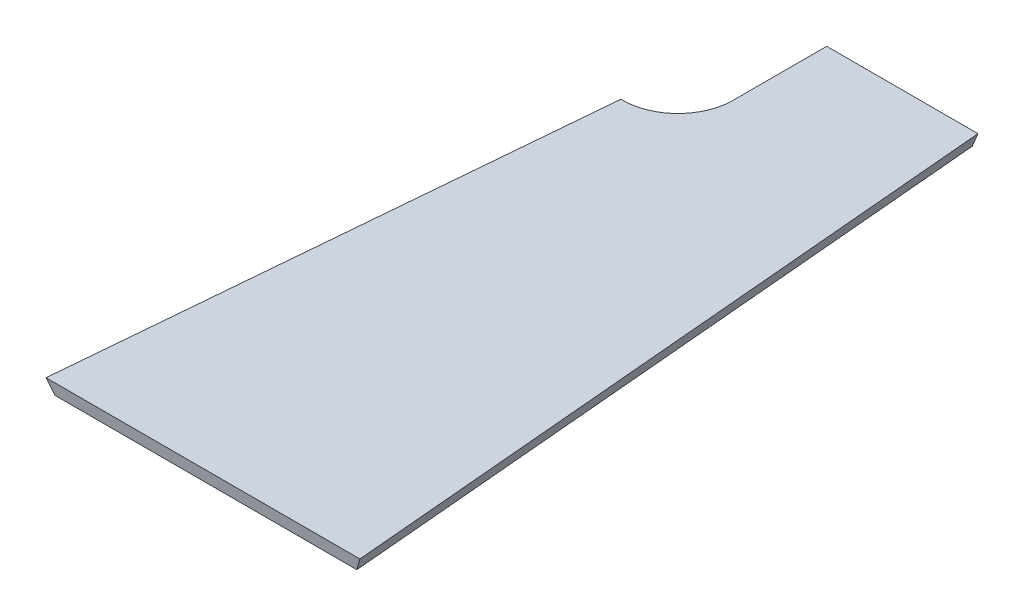
SolidWorks part; units mm, degrees
ref_plane "Ebene vorne" through (0, 0, 0) normal (0, 0, 1) x (1, 0, 0)
ref_plane "Ebene oben" through (0, 0, 0) normal (0, 1, 0) x (1, 0, 0)
ref_plane "Ebene rechts" through (0, 0, 0) normal (1, 0, 0) x (0, 0, -1)
sketch "Skizze1" plane through (0, 0, 0) normal (0, 1, 0) x (1, 0, 0)
  line L1 (-28.5, -61.5) -> (28.5, -61.5)
  line L2 (-28.5, -61.5) -> (-28.5, 61.5)
  line L3 (-28.5, 61.5) -> (28.5, 61.5)
  line L4 (28.5, -61.5) -> (28.5, 61.5)
  line L5 (-28.5, -61.5) -> (28.5, 61.5) construction
  line L6 (-28.5, 61.5) -> (28.5, -61.5) construction
  point P0 (0, 0)
  dimension "D1" = 57
  dimension "D2" = 123
extrude "Aufsatz-Linear austragen1" add sketch "Skizze1" along normal blind 2.5
sketch "Skizze2" plane through (28.5, 0, 0) normal (1, 0, 0) x (0, 0, -1)
  line L0 (-61.5, 2.5) -> (-61.5, 0)
  line L1 (55, 0) -> (-55, 0) construction
  line L2 (-61.5, 2.5) -> (-61.5, 0) construction
  line L3 (-61.5, 0) -> (-60.9686, 0)
  line L4 (-60.9686, 0) -> (-61.5, 2.5)
  dimension "D1" = 102
extrude "Schnitt-Linear austragen1" cut sketch "Skizze2" against normal through all
sketch "Skizze3" plane through (0, 2.5, 0) normal (0, 1, 0) x (1, 0, 0)
  line L0 (-28.5, -61.5) -> (-17.7389, 61.5)
  line L1 (28.5, 61.5) -> (-28.5, 61.5) construction
  line L2 (-17.7389, 61.5) -> (-28.5, 61.5)
  line L3 (-28.5, 61.5) -> (-28.5, -61.5)
  line L4 (28.5, -61.5) -> (17.7389, 61.5)
  line L5 (17.7389, 61.5) -> (28.5, 61.5)
  line L6 (28.5, 61.5) -> (28.5, -61.5)
  dimension "D1" = 95
  dimension "D2" = 95
extrude "Schnitt-Linear austragen2" cut sketch "Skizze3" against normal through all
ref_axis "Achse1" through (23.1194, 2.5, 0) along (0, -1, 0)
ref_plane "Ebene1" through (0.1756, 0, 2.0073) normal (0.0872, 0, 0.9962) x (0, -1, 0)
sketch "Skizze5" plane through (0.1756, 0, 2.0073) normal (0.0872, 0, 0.9962) x (0, -1, 0)
  line L0 (0.0086, 23.0315) -> (-2.5, 23.0315)
  line L1 (-2.5, 23.0315) -> (0, 23.0315) construction
  line L5 (0.0086, 23.0315) -> (0, 21.9959)
  line L6 (0, -33.659) -> (0, 23.0315) construction
  line L7 (0, 21.9959) -> (-2.5, 23.0315)
  line L8 (-2.5, -33.7516) -> (-2.5, 23.0315) construction
  dimension "D1" = 67.5
extrude "Schnitt-Linear austragen3" cut sketch "Skizze5" against normal through all and the other way through all
ref_axis "Achse2" through (-23.0962, 0, -0.2657) along (0, 1, 0)
ref_plane "Ebene2" through (-0.1524, 0, 1.7416) normal (-0.0872, 0, 0.9962) x (0, 1, 0)
sketch "Skizze6" plane through (-0.1524, 0, 1.7416) normal (-0.0872, 0, 0.9962) x (0, 1, 0)
  line L1 (2.5, 23.0315) -> (0, 21.9959)
  line L2 (0, -55) -> (0, 55) construction
  line L3 (0, 21.9959) -> (0, 23.0315)
  line L4 (0, 23.0315) -> (2.5, 23.0315)
  line L5 (2.5, 23.0315) -> (2.5, -33.7516) construction
  dimension "D1" = 67.5
extrude "Schnitt-Linear austragen4" cut sketch "Skizze6" against normal through all and the other way through all
sketch "Skizze7" plane through (0, 2.5, 0) normal (0, 1, 0) x (1, 0, 0)
  line L0 (-9.7389, 61.5) -> (-9.7389, 44.5)
  line L1 (17.7389, 61.5) -> (-17.7389, 61.5) construction
  line L2 (-19.7389, 34.5) -> (-20.1011, 34.5)
  line L3 (-28.5, -61.5) -> (-17.7389, 61.5) construction
  line L4 (-20.1011, 34.5) -> (-17.7389, 61.5)
  line L5 (-17.7389, 61.5) -> (-9.7389, 61.5)
  arc A0 (-19.7389, 34.5) -> (-9.7389, 44.5) centre (-19.7389, 44.5) ccw
  dimension "D1" = 10
  dimension "D2" = 17
  dimension "D3" = 8
extrude "Schnitt-Linear austragen5" cut sketch "Skizze7" against normal through all
